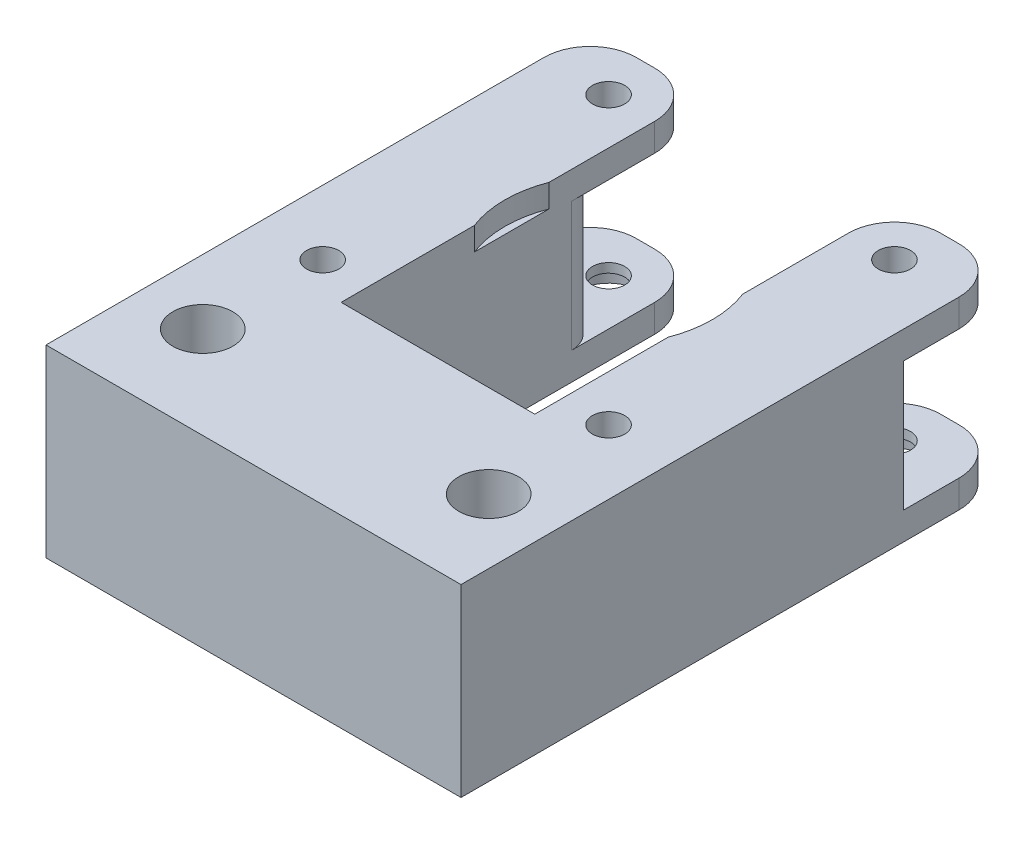
SolidWorks part; units mm, degrees
material "ABS"
ref_plane "Front Plane" through (0, 0, 0) normal (0, 0, 1) x (1, 0, 0)
ref_plane "Top Plane" through (0, 0, 0) normal (0, 1, 0) x (1, 0, 0)
ref_plane "Right Plane" through (0, 0, 0) normal (1, 0, 0) x (0, 0, -1)
sketch "Sketch1" plane through (0, 0, 0) normal (0, 1, 0) x (1, 0, 0)
  line L1 (-22.5, -10) -> (22.5, -10)
  line L2 (-22.5, -10) -> (-22.5, 10)
  line L3 (-22.5, 10) -> (22.5, 10)
  line L4 (22.5, -10) -> (22.5, 10)
  line L5 (-22.5, -10) -> (22.5, 10) construction
  line L6 (-22.5, 10) -> (22.5, -10) construction
  point P0 (0, 0)
  dimension "D1" = 20
  dimension "D2" = 45
extrude "Boss-Extrude1" add sketch "Sketch1" along normal blind 20
sketch "Sketch2" plane through (0, 0, -10) normal (0, 0, -1) x (-1, 0, 0)
  line L0 (-22.5, 20) -> (-22.5, 0) construction
  line L1 (-22.5, 20) -> (-10.5, 20)
  line L2 (-22.5, 20) -> (-22.5, 0)
  line L3 (-22.5, 0) -> (-10.5, 0)
  line L4 (-10.5, 20) -> (-10.5, 0)
  line L5 (-22.5, 20) -> (22.5, 20) construction
  line L11 (22.5, 20) -> (10.5, 20)
  line L12 (22.5, 20) -> (22.5, 0)
  line L13 (22.5, 0) -> (10.5, 0)
  line L14 (10.5, 20) -> (10.5, 0)
  dimension "D1" = 20
  dimension "D2" = 12
  dimension "D3" = 12
  dimension "D4" = 20
extrude "Boss-Extrude2" add sketch "Sketch2" along normal blind 40
sketch "Sketch3" plane through (0, 20, 0) normal (0, 1, 0) x (1, 0, 0)
  line L1 (22.5, -10) -> (22.5, 50) construction
  line L2 (10.5, 10) -> (-10.5, 10) construction
  circle A0 centre (15.5, 44) radius 1.75
  circle A1 centre (15.5, 13) radius 1.75
  circle A2 centre (-15.5, 13) radius 1.75
  circle A3 centre (-15.5, 44) radius 1.75
  dimension "D1" = 3.5
  dimension "D3" = 3.5
  dimension "D6" = 3.5
  dimension "D7" = 3.5
  dimension "D2" = 7
  dimension "D4" = 3
  dimension "D5" = 31
  dimension "D8" = 31
extrude "Cut-Extrude1" cut sketch "Sketch3" against normal through all
sketch "Sketch4" plane through (0, 20, 0) normal (0, 1, 0) x (1, 0, 0)
  line L0 (22.5, -10) -> (22.5, 50) construction
  line L1 (-22.5, 50) -> (-22.5, -10) construction
  circle A0 centre (-15.5, 0) radius 1.75
  circle A1 centre (15.5, 0) radius 1.75
  dimension "D1" = 3.5
  dimension "D2" = 3.5
  dimension "D3" = 7
  dimension "D4" = 7
extrude "Cut-Extrude2" cut sketch "Sketch4" against normal blind 25
hole_wizard "CBORE for M3 Hex Socket Head Cap Screw1" positions "Sketch5" profile "Sketch6" counterbore size "M3" standard "ISO" end condition through all
sketch "Sketch5" plane through (0, 20, 0) normal (0, 1, 0) x (1, 0, 0)
  point P0 (15.5, 0)
  point P3 (-15.5, 0)
sketch "Sketch6" plane through (15.5, 20, 0) normal (1, 0, 0) x (0, 0, 1)
  line L0 (0, 0) -> (0, 20)
  line L1 (0, 20) -> (1.75, 20)
  line L3 (1.75, 20) -> (1.75, 11.4)
  line L4 (1.75, 11.4) -> (3.25, 11.4)
  line L5 (3.25, 11.4) -> (3.25, 0)
  line L7 (3.25, 0) -> (0, 0)
  line L11 (0, -6.35) -> (0, 107.95) construction
  dimension "Thru Hole Dia." = 3.5
  dimension "Thru Hole Depth" = 20
  dimension "C'Bore Dia." = 6.5
  dimension "C'Bore Depth" = 11.4
hole_wizard "CBORE for M3 Hex Socket Head Cap Screw2" positions "Sketch7" profile "Sketch8" counterbore size "M3" standard "ISO" end condition through all
sketch "Sketch7" plane through (0, 0, 0) normal (0, -1, 0) x (-1, 0, 0)
  point P0 (15.5, 44)
  point P3 (15.5, 13)
  point P6 (-15.5, 13)
  point P9 (-15.5, 44)
sketch "Sketch8" plane through (-15.5, 0, -44) normal (1, 0, 0) x (0, 0, -1)
  line L0 (0, 0) -> (0, 20)
  line L1 (0, 20) -> (1.75, 20)
  line L3 (1.75, 20) -> (1.75, 2)
  line L4 (1.75, 2) -> (3.25, 2)
  line L5 (3.25, 2) -> (3.25, 0)
  line L7 (3.25, 0) -> (0, 0)
  line L11 (0, -6.35) -> (0, 107.95) construction
  dimension "Thru Hole Dia." = 3.5
  dimension "Thru Hole Depth" = 20
  dimension "C'Bore Dia." = 6.5
  dimension "C'Bore Depth" = 2
hole_wizard "CBORE for M3 Pan Head Screw1" positions "Sketch11" profile "Sketch12" counterbore size "M3" standard "JIS" end condition through all
sketch "Sketch11" plane through (0, 0, 0) normal (0, -1, 0) x (-1, 0, 0)
  point P0 (-15.5, 13)
  point P3 (15.5, 13)
sketch "Sketch12" plane through (15.5, 0, -13) normal (1, 0, 0) x (0, 0, -1)
  line L0 (0, 0) -> (0, 20)
  line L1 (0, 20) -> (1.75, 20)
  line L3 (1.75, 20) -> (1.75, 12.4)
  line L4 (1.75, 12.4) -> (3.25, 12.4)
  line L5 (3.25, 12.4) -> (3.25, 0)
  line L7 (3.25, 0) -> (0, 0)
  line L11 (0, -6.35) -> (0, 107.95) construction
  dimension "Thru Hole Dia." = 3.5
  dimension "Thru Hole Depth" = 20
  dimension "C'Bore Dia." = 6.5
  dimension "C'Bore Depth" = 12.4
sketch "Sketch9" plane through (22.5, 0, 0) normal (1, 0, 0) x (0, 0, -1)
  line L0 (50, 20) -> (50, 0) construction
  line L1 (50, 17) -> (38, 17)
  line L2 (50, 17) -> (50, 3)
  line L3 (50, 3) -> (38, 3)
  line L4 (38, 17) -> (38, 3)
  line L5 (-10, 20) -> (50, 20) construction
  line L6 (-10, 0) -> (50, 0) construction
  dimension "D1" = 12
  dimension "D2" = 3
  dimension "D3" = 3
extrude "Cut-Extrude3" cut sketch "Sketch9" against normal through all and the other way through all
sketch "Sketch10" plane through (0, 0, -50) normal (0, 0, -1) x (-1, 0, 0)
  line L0 (22.5, 17) -> (10.5, 17) construction
  line L1 (-22.5, 3) -> (-10.5, 3)
  line L2 (-22.5, 3) -> (-22.5, 0)
  line L3 (-22.5, 0) -> (-10.5, 0)
  line L4 (-10.5, 3) -> (-10.5, 0)
  line L5 (10.5, 3) -> (22.5, 3)
  line L6 (10.5, 3) -> (10.5, 0)
  line L7 (10.5, 0) -> (22.5, 0)
  line L8 (22.5, 3) -> (22.5, 0)
  line L9 (-22.5, 20) -> (-10.5, 20)
  line L10 (-22.5, 20) -> (-22.5, 17)
  line L11 (-22.5, 17) -> (-10.5, 17)
  line L12 (-10.5, 20) -> (-10.5, 17)
  line L13 (10.5, 20) -> (22.5, 20)
  line L14 (10.5, 20) -> (10.5, 17)
  line L15 (10.5, 17) -> (22.5, 17)
  line L16 (22.5, 20) -> (22.5, 17)
extrude "Cut-Extrude5" cut sketch "Sketch10" against normal blind 1
fillet "Fillet2" radius 5 8 edges at (-10.5, 1.5, -49) (10.5, 1.5, -49) (-10.5, 18.5, -49) (10.5, 18.5, -49) (-22.5, 18.5, -49) (-22.5, 1.5, -49) (22.5, 1.5, -49) (22.5, 18.5, -49)
fillet "Fillet5" radius 3 2 edges at (-10.5, 10, -38) (10.5, 10, -38)
sketch "Sketch13" plane through (0, 20, 0) normal (0, 1, 0) x (1, 0, 0)
  line L0 (-15.5, 13) -> (15.5, 44) construction
  circle A0 centre (0, 28.5) radius 11.25
  dimension "D1" = 22.5
extrude "Cut-Extrude6" cut sketch "Sketch13" against normal blind 2.5
